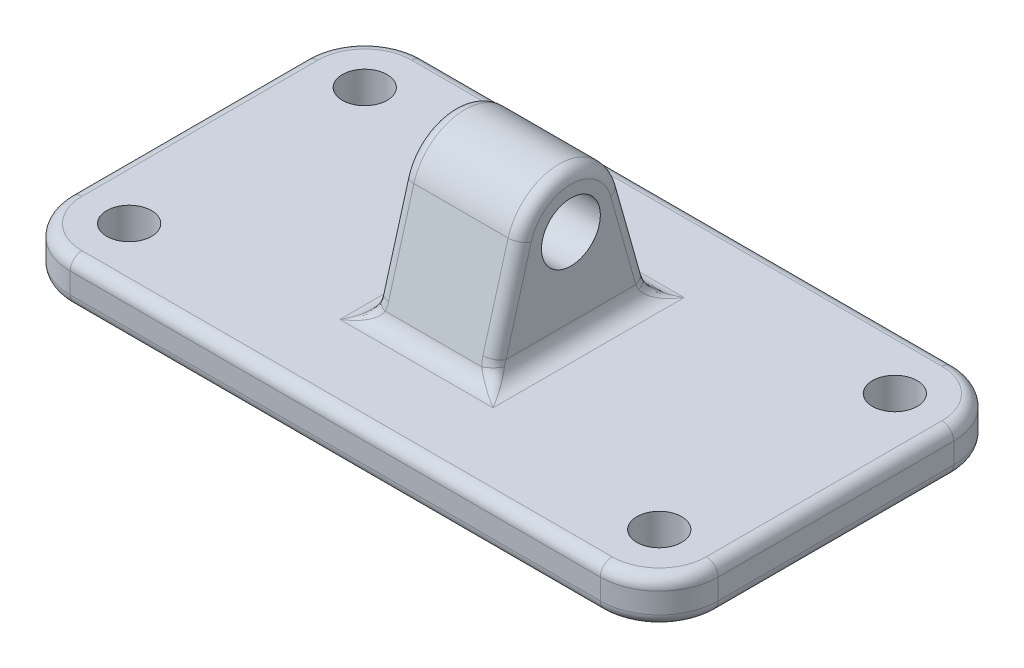
SolidWorks part; units mm, degrees
ref_plane "Front Plane" through (0, 0, 0) normal (0, 0, 1) x (1, 0, 0)
ref_plane "Top Plane" through (0, 0, 0) normal (0, 1, 0) x (1, 0, 0)
ref_plane "Right Plane" through (0, 0, 0) normal (1, 0, 0) x (0, 0, -1)
sketch "Sketch1" plane through (0, 0, 0) normal (0, 1, 0) x (1, 0, 0)
  line L0 (-57.15, 25.4) -> (57.15, 25.4) construction
  line L1 (-69.85, 38.1) -> (69.85, 38.1)
  line L2 (-69.85, 38.1) -> (-69.85, -38.1)
  line L3 (-69.85, -38.1) -> (69.85, -38.1)
  line L4 (69.85, 38.1) -> (69.85, -38.1)
  line L5 (-69.85, 38.1) -> (69.85, -38.1) construction
  line L6 (-69.85, -38.1) -> (69.85, 38.1) construction
  line L7 (57.15, 25.4) -> (57.15, -25.4) construction
  line L8 (-57.15, -25.4) -> (57.15, -25.4) construction
  line L9 (-57.15, 25.4) -> (-57.15, -25.4) construction
  circle A0 centre (-57.15, 25.4) radius 4.826
  circle A1 centre (-57.15, -25.4) radius 4.826
  circle A2 centre (57.15, -25.4) radius 4.826
  circle A3 centre (57.15, 25.4) radius 4.826
  point P0 (0, 0)
  point P14 (0, 0)
  point P15 (0, 0)
  point P16 (-57.15, -25.4)
  dimension "D4" = 9.652
  dimension "D1" = 139.7
  dimension "D2" = 76.2
  dimension "D3" = 12.7
extrude "Boss-Extrude1" add sketch "Sketch1" along normal mid plane 9.525
sketch "Sketch2" plane through (0, 0, 0) normal (1, 0, 0) x (0, 0, -1)
  line L0 (-19.05, 0) -> (19.05, 0)
  line L2 (10.9998, 28.5063) -> (19.05, 0)
  line L3 (-10.9998, 28.5063) -> (-19.05, 0)
  line L4 (0, 19.05) -> (0, 25.4) construction
  circle A0 centre (0, 25.4) radius 6.35
  arc A1 (10.9998, 28.5063) -> (-10.9998, 28.5063) centre (0, 25.4) ccw
  point P1 (0, 0)
  point P2 (0, 0)
  point P4 (0, 0)
  point P12 (0, 0)
  point P13 (0, 0)
  dimension "D3" = 12.7
  dimension "D4" = 22.86
  dimension "D1" = 38.1
extrude "Boss-Extrude2" add sketch "Sketch2" along normal mid plane 25.4
fillet "Fillet1" radius 12.7 4 edges at (-69.85, 0, 38.1) (-69.85, 0, -38.1) (69.85, 0, -38.1) (69.85, 0, 38.1)
fillet "Fillet2" radius 2.54 16 edges at (-66.1303, -4.7625, 34.3803) (-69.85, -4.7625, 0) (-66.1303, -4.7625, -34.3803) (0, -4.7625, -38.1) (66.1303, -4.7625, -34.3803) (69.85, -4.7625, 0) (66.1303, -4.7625, 34.3803) (-66.1303, 4.7625, 34.3803) (-69.85, 4.7625, 0) (-66.1303, 4.7625, -34.3803) (0, 4.7625, -38.1) (66.1303, 4.7625, -34.3803) (69.85, 4.7625, 0) (66.1303, 4.7625, 34.3803) (0, -4.7625, 38.1) (0, 4.7625, 38.1)
fillet "Fillet3" radius 3.81 4 edges at (-12.7, 4.7625, 0) (0, 4.7625, -17.7051) (12.7, 4.7625, 0) (0, 4.7625, 17.7051)
fillet "Fillet4" radius 2.54 14 edges at (-14.211, 5.5343, -18.2891) (-12.736, 8.0498, -16.7767) (-12.7, 18.5394, -13.8145) (-12.7, 36.83, 0) (-14.211, 5.5343, 18.2891) (-12.736, 8.0498, 16.7767) (14.211, 5.5343, -18.2891) (12.736, 8.0498, -16.7767) (12.7, 18.5394, -13.8145) (12.7, 36.83, 0) (14.211, 5.5343, 18.2891) (12.736, 8.0498, 16.7767) (-12.7, 18.5394, 13.8145) (12.7, 18.5394, 13.8145)
